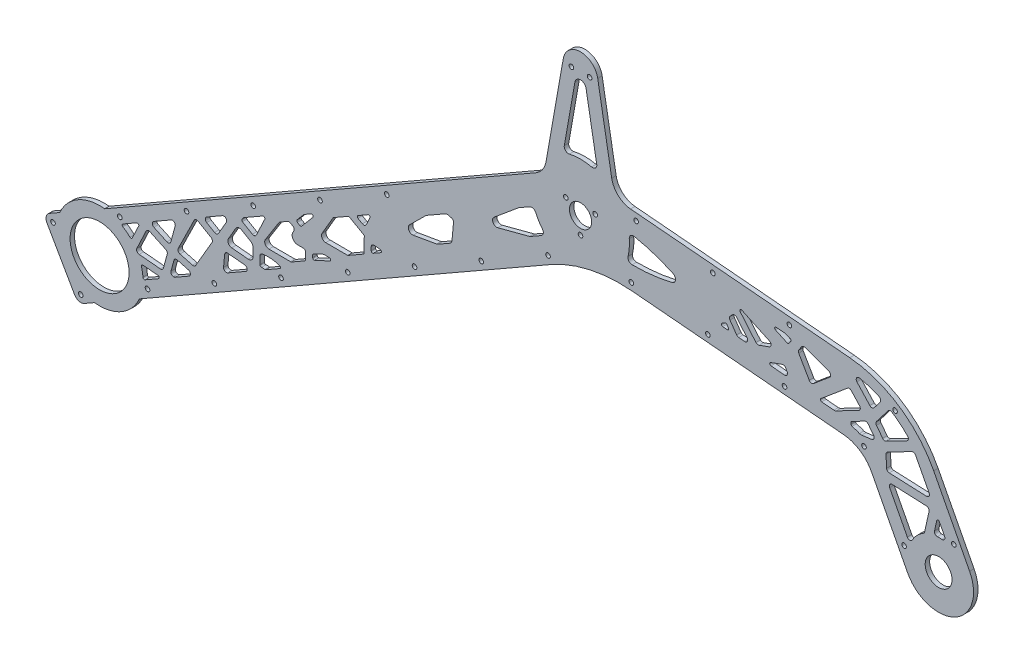
SolidWorks part; units mm, degrees
material "6061-T6 (SS)"
ref_plane "Front Plane" through (0, 0, 0) normal (0, 0, 1) x (1, 0, 0)
ref_plane "Top Plane" through (0, 0, 0) normal (0, 1, 0) x (1, 0, 0)
ref_plane "Right Plane" through (0, 0, 0) normal (1, 0, 0) x (0, 0, -1)
sketch "Reference Sketch" plane through (0, 0, 0) normal (0, 0, 1) x (1, 0, 0)
  line L0 (-343.92, -196.825) -> (0, 0) construction
  line L1 (-243.92, 103.175) -> (356.08, 103.175) construction
  line L2 (-243.92, 103.175) -> (-243.92, 0) construction
  line L3 (-243.92, 0) -> (356.08, 0) construction
  line L4 (356.08, 103.175) -> (356.08, 0) construction
  line L5 (0, 0) -> (256.08, -92.7116) construction
  line L6 (256.08, -92.7116) -> (56.08, -196.825) construction
  line L7 (256.08, -92.7116) -> (456.08, -196.825) construction
  line L8 (-343.92, -196.825) -> (56.08, -196.825) construction
  line L9 (56.08, -196.825) -> (456.08, -196.825) construction
  circle A1 centre (-343.92, -196.825) radius 100 construction
  circle A2 centre (56.08, -196.825) radius 100 construction
  circle A3 centre (456.08, -196.825) radius 100 construction
  circle A4 centre (-343.92, -196.825) radius 16.05 construction
  circle A5 centre (-343.92, -196.825) radius 28.55 construction
  circle A6 centre (-343.92, -196.825) radius 38.55 construction
  circle A7 centre (-343.92, -196.825) radius 33.55 construction
  point P13 (-343.92, -296.825)
  point P14 (556.08, -196.825)
  point P17 (-443.92, -196.825)
  dimension "D3" = 32.1
  dimension "D5" = 200
  dimension "D9" = 57.1
  dimension "D10" = 10
  dimension "D11" = 5
  dimension "D1" = 600
  dimension "D2" = 103.175
  dimension "D4" = 243.92
  dimension "D6" = 125
  dimension "D7" = 400
  dimension "D8" = 1000
sketch "Sketch2" plane through (0, 0, 0) normal (0, 0, 1) x (1, 0, 0)
  line L0 (-379.7168, -188.5069) -> (-32.0065, 10.4873)
  line L1 (-354.8814, -231.9028) -> (-21.5627, -41.1449)
  line L2 (-343.92, -196.825) -> (0, 0) construction
  line L3 (-184.3777, -76.7146) -> (-159.5423, -120.1104) construction
  line L4 (-24.685, 20.9013) -> (-12.3101, 91.0831)
  line L5 (12.3101, 91.0831) -> (22.322, 34.3028)
  line L6 (0, 98.4125) -> (0, 112.7) construction
  line L7 (-5.4848, 79.4125) -> (5.4848, 79.4125) construction
  line L8 (5.4848, 79.4125) -> (10.9697, 88.9125) construction
  line L9 (10.9697, 88.9125) -> (5.4848, 98.4125) construction
  line L10 (5.4848, 98.4125) -> (-5.4848, 98.4125) construction
  line L11 (-5.4848, 98.4125) -> (-10.9697, 88.9125) construction
  line L12 (-10.9697, 88.9125) -> (-5.4848, 79.4125) construction
  line L13 (-243.92, 103.175) -> (356.08, 103.175) construction
  line L14 (0, 88.9125) -> (0, 0) construction
  line L15 (35.7868, 21.9646) -> (192.5861, 8.2464)
  line L16 (252.5753, -31.8371) -> (278.2553, -81.1679)
  line L17 (233.9047, -104.2553) -> (208.2247, -54.9245)
  line L18 (36.8237, -28.3172) -> (188.2284, -41.5633)
  line L19 (0, 0) -> (192.5861, -16.8491) construction
  line L21 (-365.6311, -190.9191) -> (-338.0141, -175.1139) construction
  line L22 (-381.5729, -195.33) -> (-361.7045, -230.0467)
  line L23 (256.08, -92.7116) -> (56.08, -196.825) construction
  line L25 (-243.92, 0) -> (356.08, 0) construction
  circle A0 centre (0, 0) radius 7.9375
  circle A1 centre (-343.92, -196.825) radius 16.05
  arc A3 (-12.3101, 91.0831) -> (12.3101, 91.0831) centre (0, 88.9125) cw
  circle A4 centre (0, 88.9125) radius 6.5 construction
  circle A5 centre (-6.5, 88.9125) radius 1.65
  circle A6 centre (6.5, 88.9125) radius 1.65
  circle A7 centre (0, 88.9125) radius 9.5 construction
  arc A8 (252.5753, -31.8371) -> (192.5861, 8.2464) centre (186.0495, -66.4682) ccw
  circle A9 centre (256.08, -92.7116) radius 9.5885
  arc A10 (278.2553, -81.1679) -> (233.9047, -104.2553) centre (256.08, -92.7116) cw
  arc A11 (-21.5627, -41.1449) -> (36.8237, -28.3172) centre (28.1082, -127.9366) cw
  arc A12 (188.2284, -41.5633) -> (208.2247, -54.9245) centre (186.0495, -66.4682) cw
  arc A13 (22.322, 34.3028) -> (35.7868, 21.9646) centre (37.0941, 36.9075) ccw
  arc A14 (-32.0065, 10.4873) -> (-24.685, 20.9013) centre (-39.4572, 23.506) ccw
  circle A17 centre (-343.92, -196.825) radius 22.5 construction
  circle A18 centre (-365.6311, -190.9191) radius 1.65
  circle A19 centre (-338.0141, -175.1139) radius 1.65
  circle A20 centre (-322.2089, -202.7309) radius 1.65
  circle A21 centre (-349.8259, -218.5361) radius 1.65
  arc A27 (-379.7168, -188.5069) -> (-381.5729, -195.33) centre (-377.2333, -192.8465) ccw
  arc A28 (-361.7045, -230.0467) -> (-354.8814, -231.9028) centre (-357.3649, -227.5632) ccw
  circle A29 centre (-343.92, -196.825) radius 33.55 construction
  circle A32 centre (-343.92, -196.825) radius 38.55 construction
  point P16 (-171.96, -98.4125)
  point P64 (-343.92, -196.825)
  dimension "D1" = 15.875
  dimension "D2" = 32.1
  dimension "D3" = 45
  dimension "D5" = 13
  dimension "D6" = 3.3
  dimension "D7" = 6
  dimension "D12" = 50
  dimension "D14" = 100
  dimension "D16" = 15
  dimension "D17" = 5
  dimension "D18" = 25
  dimension "D19" = 3.3
  dimension "D15" = 4
  dimension "D20" = 19.177
  dimension "D4" = 50
  dimension "D8" = 19
  dimension "D9" = 14.2875
  dimension "D10" = 9.525
  dimension "D11" = 10
  dimension "D13" = 50
extrude "Base" add sketch "Sketch2" along normal blind 3.175
sketch "Sketch3" plane through (0, 0, 3.175) normal (0, 0, 1) x (1, 0, 0)
  line L0 (-343.92, -196.825) -> (0, 0) construction
  line L5 (0, 0) -> (197.3986, -17.2701) construction
  line L6 (192.5861, 8.2464) -> (35.7868, 21.9646) construction
  line L7 (0, 0) -> (-23.2167, -36.3305) construction
  line L8 (145.8888, -32.84) -> (188.6641, -36.5824) construction
  line L9 (36.8237, -28.3172) -> (188.2284, -41.5633) construction
  line L10 (212.6598, -52.6158) -> (231.4136, -88.6414) construction
  line L11 (0, 0) -> (36.3074, -23.2529) construction
  line L12 (231.4136, -88.6414) -> (266.894, -70.1715) construction
  line L13 (266.894, -70.1715) -> (248.1402, -34.1458) construction
  line L14 (192.1504, 3.2654) -> (149.375, 7.0078) construction
  line L15 (208.2247, -54.9245) -> (233.9047, -104.2553) construction
  circle A0 centre (-357.3649, -227.5632) radius 1.65
  circle A1 centre (-343.92, -196.825) radius 33.55 construction
  arc A2 (-361.7045, -230.0467) -> (-354.8814, -231.9028) centre (-357.3649, -227.5632) ccw construction
  circle A3 centre (-309.6295, -200.2442) radius 1.65
  circle A4 centre (-261.894, -172.9253) radius 1.65
  circle A5 centre (-214.1585, -145.6063) radius 1.65
  circle A6 centre (-166.4231, -118.2874) radius 1.65
  circle A7 centre (-118.6876, -90.9684) radius 1.65
  circle A8 centre (-329.4978, -165.5275) radius 1.65
  circle A9 centre (-377.2333, -192.8465) radius 1.65
  circle A10 centre (-281.7623, -138.2086) radius 1.65
  circle A11 centre (-234.0269, -110.8896) radius 1.65
  circle A12 centre (-186.2914, -83.5707) radius 1.65
  circle A13 centre (-138.5559, -56.2517) radius 1.65
  circle A14 centre (36.3074, -23.2529) radius 1.65
  circle A15 centre (91.0981, -28.0464) radius 1.65
  circle A16 centre (145.8888, -32.84) radius 1.65
  circle A17 centre (149.375, 7.0078) radius 1.65
  circle A18 centre (94.5843, 11.8013) radius 1.65
  circle A19 centre (39.7936, 16.5949) radius 1.65
  circle A20 centre (-70.9521, -63.6495) radius 1.65
  circle A21 centre (-23.2167, -36.3305) radius 1.65
  arc A22 (188.6641, -36.5824) -> (212.6598, -52.6158) centre (186.0495, -66.4682) cw construction
  arc A23 (248.1402, -34.1458) -> (192.1504, 3.2654) centre (186.0495, -66.4682) ccw construction
  arc A24 (252.5753, -31.8371) -> (192.5861, 8.2464) centre (186.0495, -66.4682) ccw construction
  arc A25 (208.2247, -54.9245) -> (188.2284, -41.5633) centre (186.0495, -66.4682) ccw construction
  circle A26 centre (202.7166, -41.5241) radius 1.65
  circle A27 centre (224.9394, -8.2653) radius 1.65
  circle A28 centre (231.4136, -88.6414) radius 1.65
  circle A29 centre (266.894, -70.1715) radius 1.65
  circle A30 centre (256.08, -92.7116) radius 9.5885 construction
  dimension "D1" = 3.3
  dimension "D2" = 8
  dimension "D3" = 5
  dimension "D5" = 3
  dimension "D7" = 15
  dimension "D4" = 55
  dimension "D6" = 55
extrude "Strut Holes" cut sketch "Sketch3" against normal through all
sketch "Sketch6" plane through (0, 0, 3.175) normal (0, 0, 1) x (1, 0, 0)
  line L0 (-315.2692, -197.7109) -> (-301.7593, -189.9792)
  line L1 (-354.8814, -231.9028) -> (-21.5627, -41.1449) construction
  line L2 (-289.845, -183.1607) -> (-279.9388, -177.4914)
  line L3 (-225.0683, -146.089) -> (-215.0659, -140.3647)
  line L4 (-202.4189, -105.5114) -> (-200.6862, -106.5205)
  line L5 (-330.4255, -170.6672) -> (-317.3783, -163.2003)
  line L6 (-32.0065, 10.4873) -> (-379.7168, -188.5069) construction
  line L7 (-315.9769, -164.4942) -> (-323.4022, -180.2613)
  line L8 (-325.3934, -181.4009) -> (-327.8261, -181.1787)
  line L9 (-302.165, -188.1154) -> (-317.5291, -186.7124)
  line L10 (-319.5204, -187.852) -> (-321.9207, -192.9489)
  line L11 (-295.5333, -171.6316) -> (-298.2962, -181.7883)
  line L12 (-300.4079, -183.2551) -> (-315.6625, -181.8621)
  line L13 (-317.2901, -179.0183) -> (-310.6415, -164.9005)
  line L14 (-307.9799, -163.9432) -> (-296.6111, -169.2972)
  line L15 (-280.4073, -173.8257) -> (-288.2923, -171.6808)
  line L16 (-290.7472, -173.0857) -> (-292.8686, -180.8843)
  line L17 (-292.7787, -149.122) -> (-305.2156, -156.2396)
  line L18 (-305.0743, -159.7848) -> (-295.766, -164.1685)
  line L19 (-292.984, -162.8841) -> (-289.8554, -151.3828)
  line L20 (-286.4122, -167.0105) -> (-277.4777, -169.4409)
  line L21 (-275.2245, -168.5176) -> (-263.487, -148.3649)
  line L22 (-264.2087, -145.6301) -> (-273.4911, -140.2238)
  line L23 (-276.2919, -141.0684) -> (-287.6814, -164.1971)
  line L24 (-267.3269, -134.556) -> (-255.9817, -128.0631)
  line L25 (-253.26, -130.8055) -> (-258.9575, -140.5878)
  line L26 (-261.6923, -141.3094) -> (-267.3401, -138.02)
  line L27 (-255.2613, -159.7424) -> (-254.4886, -151.2802)
  line L28 (-252.315, -149.4703) -> (-240.2297, -150.5739)
  line L29 (-292.2711, -190.3101) -> (-299.0066, -188.4038) construction
  line L30 (-252.2762, -161.6601) -> (-239.4181, -154.3014)
  line L31 (-246.5402, -131.1894) -> (-251.7948, -140.2114)
  line L32 (-249.4752, -144.7088) -> (-237.508, -145.8016)
  line L33 (-234.2352, -142.8254) -> (-234.2117, -136.6339)
  line L34 (-235.7018, -134.0302) -> (-242.4379, -130.1069)
  line L35 (-229.2226, -139.4963) -> (-229.2439, -145.1246)
  line L36 (-241.7536, -124.7193) -> (-234.6398, -128.8625)
  line L37 (-231.8238, -127.9864) -> (-225.7969, -115.1887)
  line L38 (-227.1983, -113.8948) -> (-240.4869, -121.4998)
  line L39 (-215.6688, -112.1749) -> (-225.38, -127.5855)
  line L40 (-222.8533, -132.1849) -> (-207.4544, -132.2434)
  line L41 (-206.4534, -131.9792) -> (-197.5057, -126.8584)
  line L42 (-196.4991, -125.1302) -> (-196.4845, -121.2849)
  line L43 (-198.4769, -119.2773) -> (-202.2607, -119.2629)
  line L44 (-205.6297, -113.1304) -> (-205.0269, -112.1739)
  line L45 (-205.7124, -109.3794) -> (-207.4618, -108.3605)
  line L46 (-209.4618, -108.3529) -> (-214.9702, -111.5053)
  line L47 (-223.2993, -137.1832) -> (-189.5978, -137.3112) construction
  line L48 (-199.4194, -106.3021) -> (-191.3609, -96.7721)
  line L49 (-192.6212, -95.2585) -> (-197.479, -98.0386)
  line L50 (-198.0128, -98.4831) -> (-202.6792, -104.0016)
  line L51 (-191.4798, -120.0542) -> (-191.4866, -121.8475)
  line L52 (-190.0674, -122.7592) -> (-179.2455, -117.7628)
  line L54 (-190.899, -119.1501) -> (-184.1308, -116.0253)
  line L55 (-183.2849, -115.8411) -> (-179.6609, -115.8549)
  line L56 (-166.4011, -107.9052) -> (-182.2049, -107.8452)
  line L57 (-184.7858, -103.3353) -> (-176.832, -89.6789)
  line L58 (-176.832, -89.6789) -> (-165.639, -83.2731)
  line L59 (-165.639, -83.2731) -> (-154.6405, -89.6789)
  line L60 (-154.6405, -89.6789) -> (-154.6842, -101.1996)
  line L61 (-154.6842, -101.1996) -> (-166.4011, -107.9052)
  line L62 (-176.832, -89.6789) -> (-166.4011, -107.9052) construction
  line L63 (-149.6667, -96.5998) -> (-149.6576, -94.1811)
  line L64 (-147.4757, -92.197) -> (-143.2847, -92.5797)
  line L65 (-142.8789, -94.4434) -> (-148.17, -97.4715)
  line L66 (-159.1247, -79.5451) -> (-152.014, -75.4756)
  line L67 (-150.6126, -76.7696) -> (-153.1821, -82.2258)
  line L68 (-155.9981, -83.102) -> (-159.1313, -81.2771)
  line L69 (-154.1121, -84.2004) -> (-149.6493, -91.9985) construction
  line L70 (-90.8199, -49.6985) -> (-91.8964, -61.4879)
  line L71 (-93.3939, -63.8188) -> (-101.9943, -68.7409)
  line L72 (-102.9747, -69.0935) -> (-119.6299, -71.9651)
  line L73 (-122.2529, -66.8794) -> (-110.6811, -55.3952)
  line L74 (-110.058, -54.9208) -> (-96.7247, -47.2901)
  line L75 (-94.4471, -46.9991) -> (-92.2866, -47.5868)
  line L76 (-102.4534, -69.0036) -> (-110.4008, -55.117) construction
  line L78 (-28.0968, -26.4494) -> (-35.8254, -30.8725)
  line L79 (-36.5501, -31.1694) -> (-59.134, -37.129)
  line L80 (-61.819, -31.9228) -> (-44.3172, -17.3499)
  line L81 (-43.8877, -17.0516) -> (-36.2746, -12.6946)
  line L82 (-44.1155, -17.182) -> (-36.1682, -31.0687) construction
  line L83 (-11.5997, 37.5245) -> (-3.9861, 80.7029)
  line L84 (3.9861, 80.7029) -> (11.5997, 37.5245)
  line L85 (22.322, 34.3028) -> (12.3101, 91.0831) construction
  line L86 (-12.3101, 91.0831) -> (-24.685, 20.9013) construction
  line L87 (192.5861, 8.2464) -> (35.7868, 21.9646) construction
  line L88 (36.8237, -28.3172) -> (188.2284, -41.5633) construction
  line L89 (-227.1773, -153.057) -> (-233.9128, -151.1507) construction
  line L90 (246.076, -72.9136) -> (249.254, -58.5784)
  line L91 (247.3887, -56.1475) -> (222.9622, -55.081)
  line L92 (221.1009, -58.0026) -> (233.7353, -82.273)
  line L93 (208.2247, -54.9245) -> (233.9047, -104.2553) construction
  line L94 (253.1337, -68.7997) -> (254.752, -61.5)
  line L95 (256.6153, -61.2547) -> (260.3456, -68.4206)
  line L96 (278.2553, -81.1679) -> (252.5753, -31.8371) construction
  line L97 (249.3108, -47.2228) -> (239.5975, -28.5637)
  line L98 (236.9, -27.7132) -> (219.5656, -36.7369)
  line L99 (218.491, -38.5982) -> (218.8608, -47.0688)
  line L100 (220.7717, -48.9796) -> (247.4495, -50.1444)
  line L101 (233.4135, -22.7639) -> (218.6181, -30.4658)
  line L102 (216.1079, -29.9093) -> (211.6718, -24.1281)
  line L103 (211.6718, -21.693) -> (220.0072, -10.8302)
  line L104 (209.6166, -31.3057) -> (205.7463, -26.2618)
  line L105 (203.2361, -25.7053) -> (194.0101, -30.5081)
  line L106 (193.4718, -31.3951) -> (193.4718, -32.4967)
  line L107 (201.069, -35.4569) -> (208.2909, -34.5061)
  line L108 (214.3031, -8.4078) -> (209.9577, -14.0708)
  line L109 (197.6887, -4.156) -> (206.8964, -14.2045)
  line L110 (193.6814, -11.6243) -> (199.5455, -18.0239)
  line L111 (198.9945, -21.1491) -> (182.8075, -29.5754)
  line L112 (181.1608, -29.903) -> (172.4826, -29.1438)
  line L113 (171.927, -27.3815) -> (190.9213, -11.4434)
  line L114 (178.1992, -11.0225) -> (166.5918, -20.7623)
  line L115 (163.5742, -20.2302) -> (156.048, -7.1944)
  line L116 (156.1417, -5.0472) -> (158.1885, -2.1242)
  line L117 (160.5108, -1.3919) -> (177.5977, -7.611)
  line L118 (146.6448, -20.9077) -> (147.747, -22.8167)
  line L119 (145.8406, -25.8091) -> (136.23, -24.9682)
  line L120 (135.9751, -23.0324) -> (144.2287, -20.0283)
  line L121 (134.9743, -13.819) -> (127.6718, -16.4769)
  line L122 (125.4557, -15.8831) -> (114.1985, -2.4673)
  line L123 (115.3872, -0.9182) -> (135.1355, -10.127)
  line L124 (139.4306, -1.096) -> (147.8318, -5.0136)
  line L125 (149.0736, -4.6809) -> (150.4259, -2.7496)
  line L126 (149.9488, -1.2363) -> (146.0985, 0.1651)
  line L127 (145.3339, 0.3346) -> (139.9404, 0.8065)
  line L128 (111.6605, -7.2212) -> (119.0455, -16.0223)
  line L129 (117.3391, -19.3002) -> (113.1162, -18.9308)
  line L130 (111.6522, -18.0855) -> (106.8775, -11.2665)
  line L131 (107.1016, -8.7052) -> (108.7142, -7.0926)
  line L132 (104.7039, -15.1361) -> (105.7554, -16.6377)
  line L133 (104.8491, -18.2075) -> (101.6773, -17.93)
  line L134 (101.2644, -16.0678) -> (103.3847, -14.8436)
  arc A0 (-317.584, -197.4764) -> (-320.5599, -195.9279) centre (-322.2089, -202.7309) ccw
  arc A1 (-291.1568, -183.3993) -> (-291.2348, -183.3872) centre (-292.2711, -190.3101) ccw
  arc A2 (-225.7665, -146.2006) -> (-228.1106, -146.1195) centre (-227.1773, -153.057) ccw
  arc A4 (-322.0747, -194.2209) -> (-322.0953, -194.053) centre (-343.92, -196.825) ccw
  arc A5 (-331.3132, -177.1382) -> (-331.3392, -173.0054) centre (-338.0141, -175.1139) ccw
  arc A6 (-329.0005, -180.6569) -> (-330.6088, -179.309) centre (-343.92, -196.825) ccw
  arc A8 (-227.5555, -137.5318) -> (-215.2363, -138.5515) centre (-223.3943, -162.1831) cw
  arc A9 (-241.9747, -123.1658) -> (-241.1717, -122.1478) centre (-247.0456, -118.3403) ccw
  arc A10 (-32.0383, -14.0906) -> (-27.2511, -21.9631) centre (0, 0) ccw
  arc A11 (-251.7948, -140.2114) -> (-249.4752, -144.7088) centre (-249.2024, -141.7213) ccw
  arc A12 (-225.38, -127.5855) -> (-222.8533, -132.1849) centre (-222.8419, -129.1849) ccw
  arc A13 (-182.2049, -107.8452) -> (-184.7858, -103.3353) centre (-182.1935, -104.8452) cw
  arc A14 (-119.6299, -71.9651) -> (-122.2529, -66.8794) centre (-120.1396, -69.0087) cw
  arc A15 (-59.134, -37.129) -> (-61.819, -31.9228) centre (-59.8994, -34.2283) cw
  arc A16 (-7.9627, 34.0822) -> (7.9627, 34.0822) centre (0, 0) cw
  arc A17 (-3.9861, 80.7029) -> (3.9861, 80.7029) centre (0, 80) cw
  arc A18 (34.8636, 3.0867) -> (34.0029, -8.2948) centre (0, 0) cw
  arc A19 (38.4335, 6.2944) -> (66.0977, -2.7713) centre (15.1723, -111.4295) cw
  arc A20 (66.0977, -2.7713) -> (65.4856, -8.7407) centre (64.749, -5.6491) cw
  arc A21 (36.898, -12.0057) -> (65.4856, -8.7407) centre (37.6733, 107.9918) ccw
  arc A22 (245.141, -74.2025) -> (237.26, -82.3165) centre (256.08, -92.7116) ccw
  arc A23 (258.3595, -71.3328) -> (255.1708, -71.2308) centre (256.08, -92.7116) ccw
  arc A24 (222.6875, -10.3732) -> (233.9189, -19.5905) centre (186.0495, -66.4682) cw
  arc A25 (252.5753, -31.8371) -> (192.5861, 8.2464) centre (186.0495, -66.4682) ccw construction
  arc A26 (194.2312, -33.4673) -> (199.4914, -35.2382) centre (186.0495, -66.4682) cw
  arc A27 (208.2247, -54.9245) -> (188.2284, -41.5633) centre (186.0495, -66.4682) ccw construction
  arc A28 (213.5369, -5.3663) -> (199.5667, -0.8459) centre (186.0495, -66.4682) ccw
  arc A29 (218.8608, -47.0688) -> (220.7717, -48.9796) centre (220.8589, -46.9815) ccw
  arc A30 (239.5975, -28.5637) -> (236.9, -27.7132) centre (237.8235, -29.4872) ccw
  arc A31 (219.5656, -36.7369) -> (218.491, -38.5982) centre (220.4891, -38.5109) ccw
  arc A32 (127.6718, -16.4769) -> (125.4557, -15.8831) centre (126.9878, -14.5975) cw
  arc A33 (-240.4869, -121.4998) -> (-241.1717, -122.1478) centre (-239.4934, -123.2356) ccw
  arc A34 (-234.6398, -128.8625) -> (-231.8238, -127.9864) centre (-233.6332, -127.1343) ccw
  arc A35 (-229.2226, -139.4963) -> (-227.5555, -137.5318) centre (-227.2226, -139.5039) cw
  arc A36 (-315.2692, -197.7109) -> (-317.584, -197.4764) centre (-316.2626, -195.9751) cw
  arc A37 (-322.0747, -194.2209) -> (-320.5599, -195.9279) centre (-320.0887, -193.9842) ccw
  arc A38 (-321.9207, -192.9489) -> (-322.0953, -194.053) centre (-320.1113, -193.801) ccw
  arc A39 (-317.5291, -186.7124) -> (-319.5204, -187.852) centre (-317.711, -188.7042) ccw
  arc A40 (-323.4022, -180.2613) -> (-325.3934, -181.4009) centre (-325.2116, -179.4092) cw
  arc A41 (-327.8261, -181.1787) -> (-329.0005, -180.6569) centre (-327.6442, -179.187) cw
  arc A42 (-331.3132, -177.1382) -> (-330.6088, -179.309) centre (-329.3986, -177.7166) ccw
  arc A43 (-330.4255, -170.6672) -> (-331.3392, -173.0054) centre (-329.4321, -172.403) ccw
  arc A44 (-315.6625, -181.8621) -> (-317.2901, -179.0183) centre (-315.4807, -179.8704) cw
  arc A45 (-298.2962, -181.7883) -> (-300.4079, -183.2551) centre (-300.226, -181.2634) cw
  arc A46 (-289.845, -183.1607) -> (-291.1568, -183.3993) centre (-290.8384, -181.4248) cw
  arc A47 (-292.8686, -180.8843) -> (-291.2348, -183.3872) centre (-290.9387, -181.4092) ccw
  arc A48 (-280.4073, -173.8257) -> (-279.9388, -177.4914) centre (-280.9322, -175.7556) cw
  arc A49 (-288.2923, -171.6808) -> (-290.7472, -173.0857) centre (-288.8173, -173.6107) ccw
  arc A50 (-295.5333, -171.6316) -> (-296.6111, -169.2972) centre (-297.4632, -171.1066) ccw
  arc A51 (-310.6415, -164.9005) -> (-307.9799, -163.9432) centre (-308.8321, -165.7526) cw
  arc A52 (-305.2156, -156.2396) -> (-305.0743, -159.7848) centre (-304.2222, -157.9754) ccw
  arc A53 (-292.7787, -149.122) -> (-289.8554, -151.3828) centre (-291.7853, -150.8578) cw
  arc A54 (-295.766, -164.1685) -> (-292.984, -162.8841) centre (-294.9139, -162.3591) ccw
  arc A55 (-286.4122, -167.0105) -> (-287.6814, -164.1971) centre (-285.8872, -165.0807) cw
  arc A56 (-277.4777, -169.4409) -> (-275.2245, -168.5176) centre (-276.9527, -167.511) ccw
  arc A57 (-263.487, -148.3649) -> (-264.2087, -145.6301) centre (-265.2153, -147.3583) ccw
  arc A58 (-273.4911, -140.2238) -> (-276.2919, -141.0684) centre (-274.4977, -141.952) ccw
  arc A59 (-267.3269, -134.556) -> (-267.3401, -138.02) centre (-266.3335, -136.2918) ccw
  arc A60 (-258.9575, -140.5878) -> (-261.6923, -141.3094) centre (-260.6857, -139.5812) cw
  arc A61 (-254.4886, -151.2802) -> (-252.315, -149.4703) centre (-252.4969, -151.462) cw
  arc A62 (-255.2613, -159.7424) -> (-252.2762, -161.6601) centre (-253.2696, -159.9243) ccw
  arc A63 (-239.4181, -154.3014) -> (-240.2297, -150.5739) centre (-240.4115, -152.5656) ccw
  arc A64 (-255.9817, -128.0631) -> (-253.26, -130.8055) centre (-254.9883, -129.7989) cw
  arc A65 (-207.4544, -132.2434) -> (-206.4534, -131.9792) centre (-207.4468, -130.2434) ccw
  arc A66 (-214.9702, -111.5053) -> (-215.6688, -112.1749) centre (-213.9767, -113.2412) ccw
  arc A67 (-207.4618, -108.3605) -> (-209.4618, -108.3529) centre (-208.4684, -110.0887) ccw
  arc A68 (-205.0269, -112.1739) -> (-205.7124, -109.3794) centre (-206.719, -111.1076) ccw
  arc A69 (-202.2607, -119.2629) -> (-205.6297, -113.1304) centre (-202.2456, -115.263) cw
  arc A70 (-196.4845, -121.2849) -> (-198.4769, -119.2773) centre (-198.4845, -121.2773) ccw
  arc A71 (-197.5057, -126.8584) -> (-196.4991, -125.1302) centre (-198.4991, -125.1226) ccw
  arc A72 (-184.1308, -116.0253) -> (-183.2849, -115.8411) centre (-183.2925, -117.8411) cw
  arc A73 (-197.479, -98.0386) -> (-198.0128, -98.4831) centre (-196.4856, -99.7744) ccw
  arc A74 (-149.6576, -94.1811) -> (-147.4757, -92.197) centre (-147.6576, -94.1887) cw
  arc A75 (-153.1821, -82.2258) -> (-155.9981, -83.102) centre (-154.9915, -81.3737) cw
  arc A76 (-90.8199, -49.6985) -> (-92.2866, -47.5868) centre (-92.8116, -49.5167) ccw
  arc A77 (111.6605, -7.2212) -> (108.7142, -7.0926) centre (110.1284, -8.5068) ccw
  arc A78 (106.8775, -11.2665) -> (107.1016, -8.7052) centre (108.5158, -10.1194) cw
  arc A79 (113.1162, -18.9308) -> (111.6522, -18.0855) centre (113.2905, -16.9384) cw
  arc A80 (119.0455, -16.0223) -> (117.3391, -19.3002) centre (117.5134, -17.3078) cw
  arc A81 (134.9743, -13.819) -> (135.1355, -10.127) centre (134.2903, -11.9396) ccw
  arc A82 (146.6448, -20.9077) -> (144.2287, -20.0283) centre (144.9128, -21.9077) ccw
  arc A83 (147.747, -22.8167) -> (145.8406, -25.8091) centre (146.0149, -23.8167) cw
  arc A84 (156.048, -7.1944) -> (156.1417, -5.0472) centre (157.78, -6.1944) cw
  arc A85 (158.1885, -2.1242) -> (160.5108, -1.3919) centre (159.8268, -3.2713) cw
  arc A86 (178.1992, -11.0225) -> (177.5977, -7.611) centre (176.9136, -9.4904) ccw
  arc A87 (166.5918, -20.7623) -> (163.5742, -20.2302) centre (165.3062, -19.2302) cw
  arc A88 (193.6814, -11.6243) -> (190.9213, -11.4434) centre (192.2068, -12.9755) ccw
  arc A89 (199.5455, -18.0239) -> (198.9945, -21.1491) centre (198.071, -19.375) cw
  arc A90 (209.9577, -14.0708) -> (206.8964, -14.2045) centre (208.371, -12.8533) cw
  arc A91 (213.5369, -5.3663) -> (214.3031, -8.4078) centre (212.7164, -7.1903) cw
  arc A92 (233.9189, -19.5905) -> (233.4135, -22.7639) centre (232.49, -20.9899) cw
  arc A93 (222.6875, -10.3732) -> (220.0072, -10.8302) centre (221.5939, -12.0477) ccw
  arc A94 (211.6718, -24.1281) -> (211.6718, -21.693) centre (213.2585, -22.9105) cw
  arc A95 (218.6181, -30.4658) -> (216.1079, -29.9093) centre (217.6946, -28.6918) cw
  arc A96 (205.7463, -26.2618) -> (203.2361, -25.7053) centre (204.1595, -27.4793) ccw
  arc A97 (209.6166, -31.3057) -> (208.2909, -34.5061) centre (208.0299, -32.5232) cw
  arc A98 (246.076, -72.9136) -> (245.141, -74.2025) centre (244.1234, -72.4807) cw
  arc A99 (249.254, -58.5784) -> (247.3887, -56.1475) centre (247.3014, -58.1456) ccw
  arc A100 (222.9622, -55.081) -> (221.1009, -58.0026) centre (222.8749, -57.0791) ccw
  arc A101 (233.7353, -82.273) -> (237.26, -82.3165) centre (235.5093, -81.3495) ccw
  arc A102 (260.3456, -68.4206) -> (258.3595, -71.3328) centre (258.5716, -69.344) cw
  arc A103 (253.1337, -68.7997) -> (255.1708, -71.2308) centre (255.0863, -69.2326) ccw
  arc A104 (249.3108, -47.2228) -> (247.4495, -50.1444) centre (247.5367, -48.1463) cw
  arc A105 (199.5667, -0.8459) -> (197.6887, -4.156) centre (199.1632, -2.8048) ccw
  arc A106 (-215.2363, -138.5515) -> (-215.0659, -140.3647) centre (-215.5626, -139.4968) cw
  arc A107 (-301.7593, -189.9792) -> (-302.165, -188.1154) centre (-302.256, -189.1113) ccw
  arc A108 (-317.3783, -163.2003) -> (-315.9769, -164.4942) centre (-316.8815, -164.0682) cw
  arc A109 (-225.7969, -115.1887) -> (-227.1983, -113.8948) centre (-226.7016, -114.7627) ccw
  arc A110 (-241.7536, -124.7193) -> (-241.9747, -123.1658) centre (-241.2503, -123.8551) cw
  arc A111 (-225.7665, -146.2006) -> (-225.0683, -146.089) centre (-225.565, -145.2211) ccw
  arc A112 (-229.2439, -145.1246) -> (-228.1106, -146.1195) centre (-228.2439, -145.1284) ccw
  arc A113 (-202.4189, -105.5114) -> (-202.6792, -104.0016) centre (-201.9156, -104.6473) cw
  arc A114 (-200.6862, -106.5205) -> (-199.4194, -106.3021) centre (-200.183, -105.6564) ccw
  arc A115 (-191.4798, -120.0542) -> (-190.899, -119.1501) centre (-190.4798, -120.058) cw
  arc A116 (-191.4866, -121.8475) -> (-190.0674, -122.7592) centre (-190.4866, -121.8513) ccw
  arc A117 (-191.3609, -96.7721) -> (-192.6212, -95.2585) centre (-192.1245, -96.1264) ccw
  arc A118 (-179.2455, -117.7628) -> (-179.6609, -115.8549) centre (-179.6647, -116.8549) ccw
  arc A119 (-152.014, -75.4756) -> (-150.6126, -76.7696) centre (-151.5173, -76.3435) cw
  arc A120 (-159.1247, -79.5451) -> (-159.1313, -81.2771) centre (-158.628, -80.413) ccw
  arc A121 (-149.6667, -96.5998) -> (-148.17, -97.4715) centre (-148.6667, -96.6036) ccw
  arc A122 (-143.2847, -92.5797) -> (-142.8789, -94.4434) centre (-143.3756, -93.5755) cw
  arc A123 (101.6773, -17.93) -> (101.2644, -16.0678) centre (101.7644, -16.9338) cw
  arc A124 (104.7039, -15.1361) -> (103.3847, -14.8436) centre (103.8847, -15.7096) ccw
  arc A125 (105.7554, -16.6377) -> (104.8491, -18.2075) centre (104.9362, -17.2113) cw
  arc A126 (114.1985, -2.4673) -> (115.3872, -0.9182) centre (114.9646, -1.8245) cw
  arc A127 (136.23, -24.9682) -> (135.9751, -23.0324) centre (136.3171, -23.972) cw
  arc A128 (139.4306, -1.096) -> (139.9404, 0.8065) centre (139.8532, -0.1897) cw
  arc A129 (172.4826, -29.1438) -> (171.927, -27.3815) centre (172.5698, -28.1476) cw
  arc A130 (194.0101, -30.5081) -> (193.4718, -31.3951) centre (194.4718, -31.3951) ccw
  arc A131 (193.4718, -32.4967) -> (194.2312, -33.4673) centre (194.4718, -32.4967) ccw
  arc A132 (254.752, -61.5) -> (256.6153, -61.2547) centre (255.7283, -61.7164) cw
  arc A133 (146.0985, 0.1651) -> (145.3339, 0.3346) centre (145.0724, -2.654) ccw
  arc A134 (199.4914, -35.2382) -> (201.069, -35.4569) centre (200.6774, -32.4826) ccw
  arc A135 (182.8075, -29.5754) -> (181.1608, -29.903) centre (181.4223, -26.9144) cw
  arc A136 (-7.9627, 34.0822) -> (-11.5997, 37.5245) centre (-8.6452, 37.0035) cw
  arc A137 (7.9627, 34.0822) -> (11.5997, 37.5245) centre (8.6452, 37.0035) ccw
  arc A138 (34.8636, 3.0867) -> (38.4335, 6.2944) centre (37.8519, 3.3513) cw
  arc A139 (34.0029, -8.2948) -> (36.898, -12.0057) centre (36.9174, -9.0058) ccw
  arc A140 (-35.8254, -30.8725) -> (-36.5501, -31.1694) centre (-37.3155, -28.2687) cw
  arc A141 (-44.3172, -17.3499) -> (-43.8877, -17.0516) centre (-42.3976, -19.6554) cw
  arc A142 (-32.0383, -14.0906) -> (-36.2746, -12.6946) centre (-34.7845, -15.2984) ccw
  arc A143 (-27.2511, -21.9631) -> (-28.0968, -26.4494) centre (-29.5869, -23.8456) cw
  arc A144 (-96.7247, -47.2901) -> (-94.4471, -46.9991) centre (-95.2346, -49.8939) cw
  arc A145 (-91.8964, -61.4879) -> (-93.3939, -63.8188) centre (-94.884, -61.2151) cw
  arc A146 (-110.6811, -55.3952) -> (-110.058, -54.9208) centre (-108.5679, -57.5245) cw
  arc A147 (-101.9943, -68.7409) -> (-102.9747, -69.0935) centre (-103.4845, -66.1371) cw
  arc A148 (-246.5402, -131.1894) -> (-242.4379, -130.1069) centre (-243.9478, -132.6992) cw
  arc A149 (-234.2117, -136.6339) -> (-235.7018, -134.0302) centre (-237.2117, -136.6225) ccw
  arc A150 (-237.508, -145.8016) -> (-234.2352, -142.8254) centre (-237.2352, -142.8141) ccw
  arc A151 (150.4259, -2.7496) -> (149.9488, -1.2363) centre (149.6067, -2.176) ccw
  arc A152 (147.8318, -5.0136) -> (149.0736, -4.6809) centre (148.2544, -4.1073) ccw
  point P110 (-254.1648, -144.2806)
  point P113 (-228.2654, -132.1643)
  point P143 (34.9003, -2.6394)
  point P203 (218.9408, -48.8997)
  point P206 (238.674, -26.7897)
  point P211 (126.3559, -16.9559)
  point P214 (-240.9361, -121.7569)
  point P217 (-232.7537, -129.961)
  point P220 (-229.2164, -137.8704)
  point P229 (-318.9237, -186.5851)
  point P232 (-323.9988, -181.5282)
  point P235 (-328.5183, -181.1155)
  point P240 (-331.9839, -171.5591)
  point P247 (-290.5028, -183.5371)
  point P252 (-275.7482, -175.0931)
  point P255 (-290.2222, -171.1558)
  point P262 (-308.5502, -158.1479)
  point P265 (-288.588, -146.7237)
  point P268 (-293.6097, -165.184)
  point P271 (-288.7533, -166.3737)
  point P278 (-275.3444, -139.1443)
  point P281 (-270.3335, -136.2766)
  point P288 (-255.6107, -163.5684)
  point P294 (-249.5035, -124.3556)
  point P297 (-206.9185, -132.2454)
  point P300 (-215.403, -111.753)
  point P303 (-208.4596, -107.7794)
  point P308 (-209.4769, -119.2355)
  point P311 (-196.4769, -119.2849)
  point P314 (-196.5035, -126.2849)
  point P329 (110.2575, -5.5492)
  point P334 (112.1872, -18.8495)
  point P337 (122.1491, -19.721)
  point P340 (139.5116, -12.1676)
  point P345 (149.6679, -26.1439)
  point P350 (159.0687, -0.8671)
  point P353 (180.8529, -8.7958)
  point P356 (164.7659, -22.2944)
  point P363 (208.5067, -15.9618)
  point P366 (215.8118, -6.4415)
  point P369 (235.7568, -21.544)
  point P374 (210.7376, -22.9105)
  point P377 (217.1296, -31.2407)
  point P380 (204.7246, -24.9304)
  point P383 (211.7254, -34.054)
  point P390 (219.5014, -54.9299)
  point P393 (235.6626, -85.9753)
  point P396 (262.2729, -72.1228)
  point P401 (250.9103, -50.2955)
  point P406 (-213.2581, -139.3301)
  point P412 (-314.6256, -161.6249)
  point P415 (-224.4456, -112.3194)
  point P420 (-225.4089, -146.284)
  point P423 (-229.2487, -146.3704)
  point P426 (-203.4487, -104.9116)
  point P431 (-191.4774, -119.4171)
  point P434 (-191.4925, -123.4171)
  point P437 (-187.699, -92.4415)
  point P440 (-175.1502, -115.872)
  point P447 (-149.6733, -98.3319)
  point P450 (-140.1262, -92.8681)
  point P453 (98.5177, -17.6536)
  point P458 (106.9854, -18.3944)
  point P463 (131.7364, -24.5751)
  point P468 (170.0776, -28.9333)
  point P471 (193.4718, -30.7883)
  point P474 (193.4718, -33.2883)
  point P477 (255.3467, -58.8176)
  point P484 (182.0319, -29.9792)
  point P491 (34.2849, 7.0387)
  point P494 (32.91, -11.9136)
  point P505 (-24.8853, -24.6115)
  point P508 (-95.6462, -46.6729)
  point P511 (-92.0384, -63.0431)
  point P524 (-234.2477, -146.0993)
  point P527 (151.1734, -1.682)
  point P530 (148.5923, -5.3682)
  point P531 (0, 0)
  point P532 (0, 0)
  dimension "D1" = 14
  dimension "D2" = 10
  dimension "D3" = 2
  dimension "D5" = 22
  dimension "D6" = 9
  dimension "D12" = 5
  dimension "D19" = 7
  dimension "D31" = 7
  dimension "D40" = 25
  dimension "D44" = 19
  dimension "D62" = 5
  dimension "D92" = 35
  dimension "D96" = 3
  dimension "D97" = 10
  dimension "D100" = 15
  dimension "D104" = 30
  dimension "D105" = 120
  dimension "D107" = 43
  dimension "D116" = 65
  dimension "D117" = 8
  dimension "D127" = 9
  dimension "D128" = 6
  dimension "D171" = 2
  dimension "D172" = 1
  dimension "D173" = 3
  dimension "D174" = 1
  dimension "D175" = 4
  dimension "D7" = 35
  dimension "D8" = 35
  dimension "D9" = 20
  dimension "D10" = 22
  dimension "D11" = 20
  dimension "D13" = 5
  dimension "D14" = 45
  dimension "D15" = 45
  dimension "D16" = 17
  dimension "D17" = 15
  dimension "D18" = 5
  dimension "D20" = 55
  dimension "D21" = 5
  dimension "D22" = 45
  dimension "D23" = 23
  dimension "D24" = 34
  dimension "D25" = 60
  dimension "D26" = 5
  dimension "D27" = 5
  dimension "D28" = 5
  dimension "D29" = 30
  dimension "D30" = 24
  dimension "D32" = 55
  dimension "D33" = 35
  dimension "D34" = 25
  dimension "D35" = 5
  dimension "D36" = 6
  dimension "D37" = 60
  dimension "D38" = 5
  dimension "D39" = 20
  dimension "D41" = 11
  dimension "D42" = 35
  dimension "D43" = 60
  dimension "D45" = 19.5
  dimension "D46" = 5
  dimension "D47" = 5
  dimension "D48" = 30
  dimension "D49" = 5
  dimension "D50" = 14
  dimension "D51" = 13
  dimension "D52" = 8.5
  dimension "D53" = 60
  dimension "D54" = 12
  dimension "D55" = 7
  dimension "D56" = 22
  dimension "D57" = 28
  dimension "D58" = 60
  dimension "D59" = 15
  dimension "D60" = 8
  dimension "D61" = 13
  dimension "D63" = 12
  dimension "D64" = 20
  dimension "D65" = 5
  dimension "D66" = 65
  dimension "D67" = 25
  dimension "2" = 18
  dimension "D68" = 8
  dimension "D69" = 4
  dimension "D70" = 14
  dimension "D71" = 15
  dimension "D72" = 13.5
  dimension "D73" = 60
  dimension "D74" = 60
  dimension "D75" = 8
  dimension "D76" = 5
  dimension "D77" = 35
  dimension "D78" = 0.5076
  dimension "D79" = 5
  dimension "D80" = 11
  dimension "D81" = 35
  dimension "D82" = 16
  dimension "D83" = 18
  dimension "D84" = 55
  dimension "D85" = 45
  dimension "D86" = 20
  dimension "D87" = 15
  dimension "D88" = 12
  dimension "D89" = 17
  dimension "D90" = 16
  dimension "D91" = 18
  dimension "D93" = 15
  dimension "D94" = 10
  dimension "D95" = 13
  dimension "D98" = 10
  dimension "D99" = 80
  dimension "D101" = 16
  dimension "D102" = 22
  dimension "D103" = 22
  dimension "D106" = 7
  dimension "D108" = 10
  dimension "D109" = 40
  dimension "D110" = 10
  dimension "D111" = 6
  dimension "D112" = 60
  dimension "D113" = 35
  dimension "D114" = 15
  dimension "D115" = 6
  dimension "D118" = 26.5
  dimension "D119" = 6
  dimension "D120" = 85
  dimension "D121" = 85
  dimension "D122" = 32
  dimension "D123" = 21
  dimension "D124" = 80
  dimension "D125" = 75
  dimension "D126" = 6
  dimension "D129" = 10.5
  dimension "D130" = 80
  dimension "D131" = 12
  dimension "D132" = 8
  dimension "D133" = 6
  dimension "D134" = 2.5
  dimension "D135" = 100
  dimension "D136" = 11.5
  dimension "D137" = 60
  dimension "D138" = 11
  dimension "D139" = 45
  dimension "D140" = 12
  dimension "D141" = 8.5
  dimension "D142" = 12
  dimension "D143" = 18
  dimension "D144" = 80
  dimension "D145" = 21
  dimension "D146" = 60
  dimension "D147" = 60
  dimension "D148" = 15
  dimension "D149" = 12
  dimension "D150" = 18
  dimension "D151" = 25
  dimension "D152" = 9
  dimension "D153" = 12
  dimension "D154" = 6
  dimension "D155" = 15
  dimension "D156" = 20
  dimension "D157" = 10
  dimension "D158" = 13.5
  dimension "D159" = 4.5
  dimension "D160" = 45
  dimension "D161" = 14
  dimension "D162" = 5
  dimension "D163" = 10
  dimension "D164" = 16
  dimension "D165" = 50
  dimension "D166" = 18.5
  dimension "D167" = 50
  dimension "D168" = 4
  dimension "D169" = 8.5
  dimension "D170" = 35
  dimension "D176" = 124.6776
  dimension "D177" = 124.6776
  dimension "D178" = 5
  dimension "D179" = 51.6489
  dimension "D180" = 5
  dimension "D181" = 123.1958
extrude "Lightening Holes" cut sketch "Sketch6" against normal through all
sketch "Sketch7" plane through (0, 0, 3.175) normal (0, 0, 1) x (1, 0, 0)
  circle A0 centre (-343.92, -196.825) radius 16.05 construction
  circle A28 centre (-343.92, -196.825) radius 31.1
  circle A29 centre (-343.92, -196.825) radius 21.1
  dimension "D1" = 42.2
  dimension "D2" = 10
extrude "Inner Mod Extrusion" add sketch "Sketch7" against normal up to surface (3.175 mm away) up to face at (-260.7262, -135.4767, 0)
extrude "Inner Mod Cut" cut sketch "Sketch7<2>" against normal through all contours A29 region at (-343.92, -196.825, 3.175)
sketch "Sketch7<2>" plane through (0, 0, 3.175) normal (0, 0, 1) x (1, 0, 0) same geometry as "Sketch7"
sketch "Sketch8" plane through (0, 0, 3.175) normal (0, 0, 1) x (1, 0, 0)
  circle A0 centre (-10.5, 6.0622) radius 1.65
  circle A1 centre (10.5, 6.0622) radius 1.65
  circle A2 centre (0, -12.1244) radius 1.65
  point P0 (0, 0)
  point P1 (0, 0)
  point P14 (0, 0)
  dimension "D2" = 3.3
  dimension "D1" = 21
  dimension "D3" = 3
extrude "Cut-Extrude1" cut sketch "Sketch8" against normal through all
fillet "Fillet1" radius 1 4 edges at (-328.7213, -169.6918, 1.5875) (-321.2009, -175.587, 1.5875) (-312.8242, -196.3117, 1.5875) (-314.4137, -186.9969, 1.5875)
